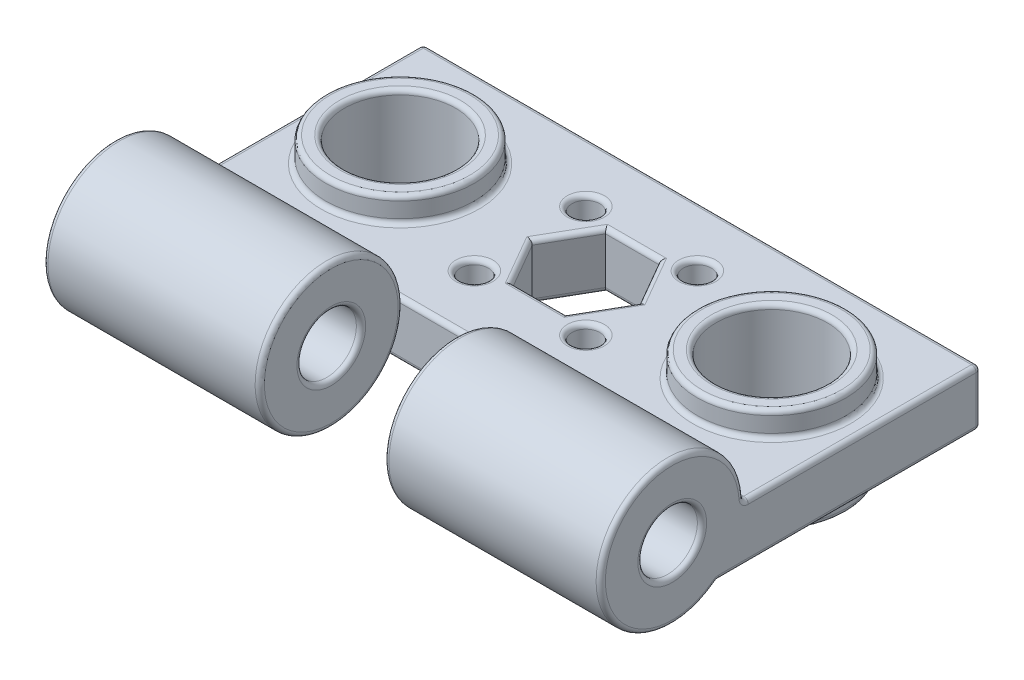
SolidWorks part; units mm, degrees
ref_plane "Front Plane" through (0, 0, 0) normal (0, 0, 1) x (1, 0, 0)
ref_plane "Top Plane" through (0, 0, 0) normal (0, 1, 0) x (1, 0, 0)
ref_plane "Right Plane" through (0, 0, 0) normal (1, 0, 0) x (0, 0, -1)
sketch "Sketch1" plane through (0, 0, 0) normal (0, 1, 0) x (1, 0, 0)
  line L0 (0, 30) -> (60, 30) construction
  line L1 (0, 0) -> (60, 0) construction
  line L2 (0, 0) -> (0, 30) construction
  line L3 (0, 30) -> (60, 30) construction
  line L4 (60, 0) -> (60, 30) construction
  line L5 (30, 30) -> (30, 0) construction
  line L6 (60, 0) -> (50, 0)
  line L7 (50, 0) -> (50, 5)
  line L8 (50, 5) -> (10, 5)
  line L9 (10, 0) -> (10, 5)
  line L10 (0, 0) -> (10, 0)
  line L11 (0, 0) -> (0, 30)
  line L12 (0, 30) -> (60, 30)
  line L13 (60, 30) -> (60, 0)
  line L14 (25.6699, 15) -> (34.3301, 20) construction
  line L15 (35.7735, 17.5) -> (32.8868, 22.5)
  line L16 (32.8868, 22.5) -> (27.1132, 22.5)
  line L17 (27.1132, 22.5) -> (24.2265, 17.5)
  line L18 (24.2265, 17.5) -> (27.1132, 12.5)
  line L19 (27.1132, 12.5) -> (32.8868, 12.5)
  line L20 (32.8868, 12.5) -> (35.7735, 17.5)
  line L21 (30, 5) -> (30, 30) construction
  line L22 (30, 17.5) -> (10, 17.5) construction
  line L24 (24, 23.5) -> (36, 23.5) construction
  line L25 (24, 23.5) -> (24, 11.5) construction
  line L26 (24, 11.5) -> (36, 11.5) construction
  line L27 (36, 23.5) -> (36, 11.5) construction
  line L28 (24, 23.5) -> (36, 11.5) construction
  line L29 (24, 11.5) -> (36, 23.5) construction
  circle A1 centre (30, 17.5) radius 5 construction
  circle A2 centre (10, 17.5) radius 6
  circle A3 centre (50, 17.5) radius 6
  circle A4 centre (36, 23.5) radius 1.5
  circle A5 centre (24, 23.5) radius 1.5
  circle A6 centre (24, 11.5) radius 1.5
  circle A7 centre (36, 11.5) radius 1.5
  point P11 (30, 5)
  point P25 (30, 17.5)
  dimension "D5" = 12
  dimension "D8" = 3
  dimension "D1" = 60
  dimension "D2" = 30
  dimension "D3" = 5
  dimension "D4" = 10
  dimension "D6" = 20
  dimension "D7" = 12
extrude "Boss-Extrude1" add sketch "Sketch1" along normal blind 6
ref_plane "Plane1" through (0, 3, 0) normal (0, 1, 0) x (1, 0, 0)
sketch "Sketch2" plane through (0, 3, 0) normal (0, 1, 0) x (1, 0, 0)
  circle A1 centre (10, 17.5) radius 6
  circle A2 centre (10, 17.5) radius 8
  circle A3 centre (10, 17.5) radius 8
  circle A4 centre (10, 17.5) radius 6 construction
  circle A6 centre (50, 17.5) radius 6
  circle A7 centre (50, 17.5) radius 8
  circle A8 centre (50, 17.5) radius 8
  dimension "D1" = 2
  dimension "D2" = 2
extrude "Boss-Extrude2" add sketch "Sketch2" along normal blind 5.65 and the other way blind 5.65
sketch "Sketch3" plane through (10, 0, 0) normal (1, 0, 0) x (0, 0, -1)
  line L0 (0, 6) -> (5, 6) construction
  line L1 (5, 6) -> (5, 0) construction
  circle A2 centre (-3.2, 6) radius 3.2
  circle A3 centre (-3.2, 6) radius 7.7
  dimension "D1" = 4.5
  dimension "D2" = 6.4
  dimension "D3" = 8.2
extrude "Boss-Extrude9" add sketch "Sketch3" along normal up to surface and the other way up to surface up to face at (60, 3, -15) other way up to face at (0, 3, -15)
ref_plane "Plane3" through (30, 0, 0) normal (1, 0, 0) x (0, 0, -1)
sketch "Sketch4" plane through (30, 0, 0) normal (1, 0, 0) x (0, 0, -1)
  circle A0 centre (-3.2, 6) radius 7.7
  arc A1 (4.5, 6) -> (1.626, 0) centre (-3.2, 6) ccw construction
extrude "Cut-Extrude1" cut sketch "Sketch4" against normal blind 6.7 and the other way blind 6.7
fillet "Fillet1" radius 0.5 60 edges at (50, 2.6736, -3.7444) (10, 2.6736, -3.7444) (36.7, 6, -4.5) (36.7, 6, 0) (60, 6, 6.4) (60, 3, -30) (60, 9.3264, 10.1444) (0, 3, -30) (0, 9.3264, 10.1444) (0, 6, 0) (30, 0, -30) (0, 0, -15.813) (5, 0, -1.626) (10, 0, -3.313) (30, 0, -5) (50, 0, -3.313) (55, 0, -1.626) (60, 0, -15.813) (36, 0, -10) (24, 0, -22) (25.6699, 0, -15) (25.6699, 0, -20) (30, 0, -22.5) (34.3301, 0, -20) (34.3301, 0, -15) (30, 0, -12.5) (36, 0, -22) (24, 0, -10) (10, 0, -25.5) (50, 0, -25.5) (50, 6, -4.75) (30, 6, -5) (10, 6, -4.75) (5, 6, -4.5) (0, 6, -17.25) (30, 6, -30) (60, 6, -17.25) (55, 6, -4.5) (36, 6, -10) (24, 6, -10) (24, 6, -22) (36, 6, -22) (34.3301, 6, -20) (30, 6, -22.5) (25.6699, 6, -20) (25.6699, 6, -15) (30, 6, -12.5) (34.3301, 6, -15) (10, 6, -25.5) (50, 6, -25.5) (23.3, 6, 0) (23.3, 6, -4.5) (10, -2.65, -9.5) (10, -2.65, -11.5) (50, -2.65, -9.5) (50, -2.65, -11.5) (50, 8.65, -11.5) (50, 8.65, -9.5) (10, 8.65, -11.5) (10, 8.65, -9.5)
